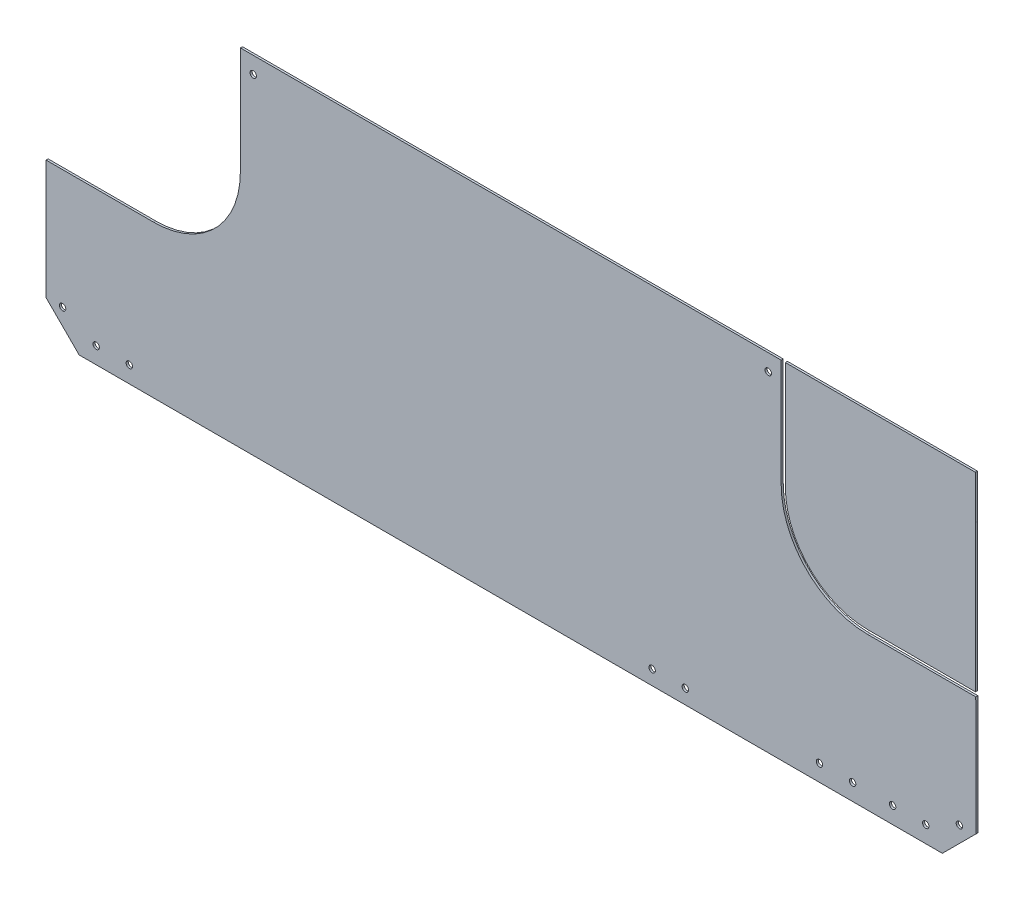
SolidWorks part; units mm, degrees
material "Perspex (TM) GS Acrylic Cast Sheet"
ref_plane "Front Plane" through (0, 0, 0) normal (0, 0, 1) x (1, 0, 0)
ref_plane "Top Plane" through (0, 0, 0) normal (0, 1, 0) x (1, 0, 0)
ref_plane "Right Plane" through (0, 0, 0) normal (1, 0, 0) x (0, 0, -1)
sketch "Sketch1" plane through (0, 0, 0) normal (0, 0, 1) x (1, 0, 0)
  line L1 (-457.2, -304.8) -> (457.2, -304.8)
  line L2 (-457.2, -304.8) -> (-457.2, 304.8)
  line L3 (-457.2, 304.8) -> (457.2, 304.8)
  line L4 (457.2, -304.8) -> (457.2, 304.8)
  line L5 (0, 304.8) -> (0, -304.8) construction
  line L6 (-457.2, 0) -> (457.2, 0) construction
  point P0 (0, 0)
  point P4 (-320.04, 0)
  point P5 (320.04, 0)
  point P6 (0, 213.36)
  point P7 (0, -213.36)
  dimension "Length" = 914.4
  dimension "Width" = 609.6
  dimension "Break" = 137.16
  dimension "D2" = 137.16
  dimension "D1" = 91.44
  dimension "D3" = 91.44
sketch "Sketch2" plane through (0, 0, 0) normal (1, 0, 0) x (0, 0, -1)
  line L0 (-0.7938, -304.8) -> (0.7938, -304.8)
  dimension "Thickness" = 1.5875
sketch "Sketch3" plane through (0, 0, 0) normal (0, 0, 1) x (1, 0, 0)
  line L0 (-457.2, -304.8) -> (-457.2, 304.8) construction
  line L1 (-457.2, -304.8) -> (457.2, -304.8) construction
  line L2 (457.2, -304.8) -> (457.2, 304.8) construction
  line L3 (-457.2, 304.8) -> (457.2, 304.8) construction
  line L4 (-457.2, -304.8) -> (-457.2, 304.8)
  line L5 (-457.2, -304.8) -> (457.2, -304.8)
  line L6 (457.2, -304.8) -> (457.2, 304.8)
  line L7 (-457.2, 304.8) -> (457.2, 304.8)
extrude "Boss-Extrude1" add sketch "Sketch3" along normal mid plane 1.5875
sketch "Sketch4" plane through (0, 0, 0.7937) normal (0, 0, 1) x (1, 0, 0)
  line L0 (-378.2467, -279.4) -> (-378.2467, -39.3705)
  line L1 (-457.2, -304.8) -> (457.2, -304.8) construction
  line L2 (-378.2467, -751.2581) -> (-378.2467, -65.4581) construction
  line L3 (-378.2467, -39.3705) -> (333.614, -39.3705)
  line L4 (333.614, -39.3705) -> (333.9807, -279.0843)
  line L5 (334.0201, -317.5147) -> (334.0201, -266.7147) construction
  line L6 (334.0201, -304.8) -> (457.2, -304.8)
  line L7 (457.2, -304.8) -> (457.2, 304.8)
  line L8 (457.2, 304.8) -> (-457.2, 304.8)
  line L9 (-457.2, 304.8) -> (-457.2, -304.8)
  line L10 (-457.2, -304.8) -> (-378.2467, -304.8)
  line L11 (-378.2467, -304.8) -> (-352.8467, -304.8)
  line L12 (-352.8467, -751.2581) -> (-352.8467, -65.4581) construction
  line L13 (-352.8467, -304.8) -> (-378.2467, -279.4)
  line L14 (334.0201, -304.8) -> (308.2651, -304.8)
  line L15 (308.2651, -39.3463) -> (308.2651, -725.1463) construction
  line L16 (308.2651, -304.8) -> (333.9807, -279.0843)
extrude "Cut-Extrude1" cut sketch "Sketch4" against normal blind 2.54
sketch "Sketch7" plane through (0, 0, 0.7937) normal (0, 0, 1) x (1, 0, 0)
  line L0 (-378.2467, -188.1903) -> (-378.2467, -39.3463)
  line L3 (-378.2467, -39.3463) -> (-229.4027, -39.3463)
  line L10 (-229.4027, -64.7463) -> (-229.4027, -39.3463)
  line L11 (-229.4027, -64.7463) -> (-229.4027, -121.8963)
  line L12 (-352.8467, -188.1903) -> (-295.6967, -188.1903)
  line L13 (-352.8467, -188.1903) -> (-378.2467, -188.1903)
  arc A1 (-229.4027, -121.8963) -> (-295.6967, -188.1903) centre (-295.6967, -121.8963) cw
extrude "Cut-Extrude2" cut sketch "Sketch7" against normal blind 2.54
sketch "Sketch8" plane through (0, 0, 0.7937) normal (0, 0, 1) x (1, 0, 0)
  line L0 (251.1151, -185.0153) -> (333.6651, -185.0153)
  line L1 (333.6651, -39.3463) -> (333.6651, -725.1463) construction
  line L2 (333.6651, -185.0153) -> (333.6651, -39.3463)
  line L3 (187.9961, -121.8963) -> (187.9961, -39.3463)
  line L4 (-378.2467, -39.3463) -> (307.5533, -39.3463) construction
  line L5 (187.9961, -39.3463) -> (333.6651, -39.3463)
  line L6 (251.1151, -188.1903) -> (336.8401, -188.1903)
  line L7 (336.8401, -188.1903) -> (336.8401, -36.1713)
  line L8 (184.8211, -36.1713) -> (336.8401, -36.1713)
  line L9 (184.8211, -121.8963) -> (184.8211, -36.1713)
  arc A0 (187.9961, -121.8963) -> (251.1151, -185.0153) centre (251.1151, -121.8963) ccw
  arc A1 (184.8211, -121.8963) -> (251.1151, -188.1903) centre (251.1151, -121.8963) ccw
  dimension "D1" = 3.175
extrude "Cut-Extrude3" cut sketch "Sketch8" against normal blind 2.54
sketch "Sketch9" plane through (0, 0, 0.7937) normal (0, 0, 1) x (1, 0, 0)
  point P0 (-365.5467, -279.4147)
  point P1 (-339.7911, -292.1147)
  point P3 (-314.3911, -292.1147)
  point P5 (-365.5467, -229.8463)
  point P15 (270.1645, -292.1147)
  point P17 (295.5645, -292.1147)
  point P19 (321.3201, -279.4147)
  point P21 (320.9651, -229.8463)
  point P23 (-219.4967, -52.0463)
  point P25 (174.9151, -52.0463)
hole_wizard "#10 (0.1935) Diameter Hole1" positions "Sketch10" profile "Sketch11" hole size "#10" standard "ANSI Inch" end condition through all
sketch "Sketch10" plane through (0, 0, 0.7937) normal (0, 0, 1) x (1, 0, 0)
  point P0 (-314.3911, -292.1147)
  point P3 (-339.7911, -292.1147)
  point P6 (-365.5467, -279.4147)
  point P21 (295.5645, -292.1147)
  point P24 (270.1645, -292.1147)
  point P27 (321.3201, -279.4147)
  point P31 (174.9151, -52.0463)
  point P34 (-219.4967, -52.0463)
  point P37 (86.0055, -293.7022)
  point P40 (111.4055, -293.7022)
  point P43 (214.1495, -292.1147)
  point P46 (239.5495, -292.1147)
sketch "Sketch11" plane through (-314.3911, -292.1147, 0.7937) normal (1, 0, 0) x (0, -1, 0)
  line L0 (0, 0) -> (0, 1.5875)
  line L1 (0, 1.5875) -> (2.4574, 1.5875)
  line L2 (2.4574, 1.5875) -> (2.4574, 0)
  line L5 (2.4574, 0) -> (0, 0)
  line L11 (0, -6.35) -> (0, 107.95) construction
  dimension "Thru Hole Dia." = 4.9149
  dimension "Thru Hole Depth" = 1.5875
equation "\"D1@Boss-Extrude1\"=\"thickness@sketch2\""
equation "\"Break@Sketch1\" = \"Length@Sketch1\" * 0.15"
equation "\"D2@Sketch1\" = \"Break@Sketch1\""
equation "\"D1@Sketch1\"=\"Width@Sketch1\"*0.15"
equation "\"D3@Sketch1\"=\"D1@Sketch1\""
